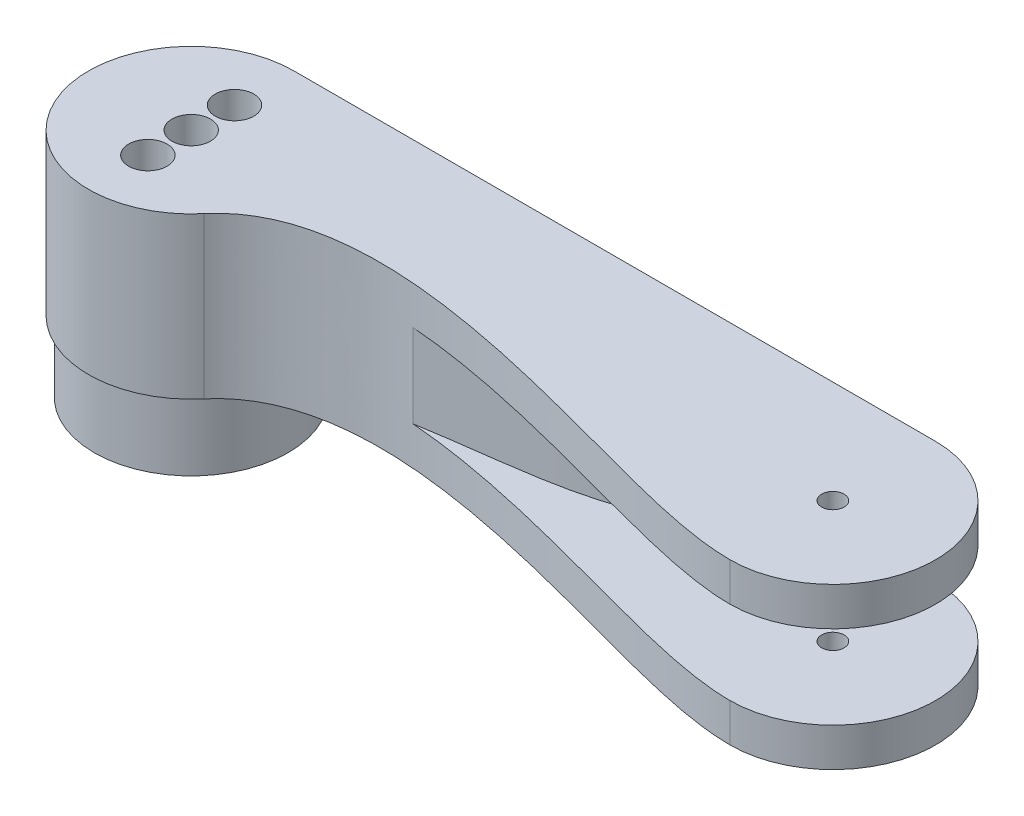
SolidWorks part; units mm, degrees
ref_plane "Front Plane" through (0, 0, 0) normal (0, 0, 1) x (1, 0, 0)
ref_plane "Top Plane" through (0, 0, 0) normal (0, 1, 0) x (1, 0, 0)
ref_plane "Right Plane" through (0, 0, 0) normal (1, 0, 0) x (0, 0, -1)
sketch "Sketch1" plane through (0, 0, 0) normal (0, 1, 0) x (1, 0, 0)
  line L0 (-50, 0) -> (50, 0) construction
  line L1 (-50, 16) -> (50, 16)
  line L2 (-50, -16) -> (50, -16)
  arc A0 (-50, 16) -> (-50, -16) centre (-50, 0) ccw
  arc A1 (50, -16) -> (50, 16) centre (50, 0) ccw
  point P3 (0, 0)
  dimension "D1" = 16
  dimension "D2" = 100
extrude "Boss-Extrude1" add sketch "Sketch1" along normal blind 6
sketch "Sketch3" plane through (0, 0, 0) normal (0, -1, 0) x (1, 0, 0)
  circle A0 centre (50, 0) radius 1.75
  dimension "D1" = 3.5
extrude "Cut-Extrude2" cut sketch "Sketch3" against normal through all
sketch "Sketch4" plane through (0, 6, 0) normal (0, 1, 0) x (1, 0, 0)
  line L0 (-50, 16) -> (30, 16)
  line L1 (-50, 16) -> (50, 16) construction
  line L4 (-34.2857, -16) -> (-50, -16)
  line L5 (-50, -16) -> (50, -16) construction
  arc A0 (-50, 16) -> (-50, -16) centre (-50, 0) ccw
  arc A1 (-50, 16) -> (-50, -16) centre (-50, 0) ccw construction
  spline S0 degree 3 poles (30, 16) (21.9929, -10.8622) (-23.6763, 6.1181) (-34.2857, -16) knots 0 0 0 0 1 1 1 1
  point P8 (-7.9869, -5.6996)
  point P13 (-50, -16)
  point P17 (-34.2857, -16)
  point P19 (-1.194, -4.2334)
  point P20 (23.7094, 6.2558)
  point P21 (-6.5401, -6.8049)
  point P22 (9.3821, 0)
  dimension "D1" = 80
extrude "Boss-Extrude2" add sketch "Sketch4" along normal blind 13
sketch "Sketch5" plane through (0, 19, 0) normal (0, 1, 0) x (1, 0, 0)
  line L0 (-50, 0) -> (50, 0) construction
  line L1 (-50, 16) -> (50, 16)
  line L2 (-50, -16) -> (50, -16)
  arc A0 (-50, 16) -> (-50, -16) centre (-50, 0) ccw
  arc A1 (50, -16) -> (50, 16) centre (50, 0) ccw
  point P4 (0, 0)
  dimension "D1" = 16
extrude "Boss-Extrude3" add sketch "Sketch5" along normal blind 6
sketch "Sketch6" plane through (0, 25, 0) normal (0, 1, 0) x (1, 0, 0)
  circle A0 centre (50, 0) radius 1.75
  dimension "D1" = 3.5
extrude "Cut-Extrude3" cut sketch "Sketch6" against normal up to next
sketch "Sketch7" plane through (0, 25, 0) normal (0, 1, 0) x (1, 0, 0)
  line L0 (0, -3.3) -> (0, 3.3) construction
  line L1 (-50, -16) -> (50, -16)
  circle A0 centre (-50, 0) radius 16
  circle A1 centre (50, 0) radius 16
  spline S0 degree 3 poles (-37.7313, -10.2703) (-30.3326, -1.4318) (6.0504, -3.3646) (38.5122, -16) (50, -16) knots 0 0 0 0 0.426661 1 1 1 1
  line M5 (-50, -16) -> (50, -16)
extrude "Cut-Extrude4" cut sketch "Sketch7" against normal up to next contours S0 A0 M5 region at (-6.9153, 25, 11.0131)
sketch "Sketch8" plane through (0, 0, 0) normal (0, -1, 0) x (1, 0, 0)
  circle A1 centre (-50, 0) radius 15.1
  dimension "D1" = 30.2
extrude "Boss-Extrude4" add sketch "Sketch8" along normal blind 11
sketch "Sketch9" plane through (0, -11, 0) normal (0, -1, 0) x (1, 0, 0)
  circle A0 centre (-50, 0) radius 6.75 construction
  circle A1 centre (-50, 6.75) radius 1.75
  circle A2 centre (-50, -6.75) radius 1.75
  arc A3 (-50, 16) -> (-50, -16) centre (-50, 0) ccw construction
  point P6 (-50, 0)
  dimension "D1" = 13.5
  dimension "D2" = 3.5
extrude "Cut-Extrude5" cut sketch "Sketch9" against normal blind 10
sketch "Sketch11" plane through (0, -11, 0) normal (0, -1, 0) x (1, 0, 0)
  circle A0 centre (-50, 0) radius 3
  dimension "D1" = 6
extrude "Cut-Extrude6" cut sketch "Sketch11" against normal up to next and the other way through all
sketch "Sketch12" plane through (0, -1, 0) normal (0, -1, 0) x (1, 0, 0)
  circle A0 centre (-50, 0) radius 6.75 construction
  circle A1 centre (-50, 6.75) radius 3
  circle A2 centre (-50, -6.75) radius 3
  circle A3 centre (-50, 6.75) radius 1.75 construction
  dimension "D1" = 6
  dimension "D3" = 13.5
  dimension "D2" = 2
extrude "Cut-Extrude7" cut sketch "Sketch12" against normal up to next
equation "\"Length\"= 100mm"
equation "\"Radius\"= 14.25mm"
equation "\"Thick\"= 12mm"
equation "\"D1@Sketch1\"=16"
equation "\"D2@Sketch1\" = \"Length\""
equation "\"D1@Boss-Extrude1\"= \"Thick\""
equation "\"D1@Sketch4\"=\"Length\"*0.8"
equation "\"D1@Sketch5\"=16"
equation "\"D1@Boss-Extrude4\"=\"Thick\"-1"
